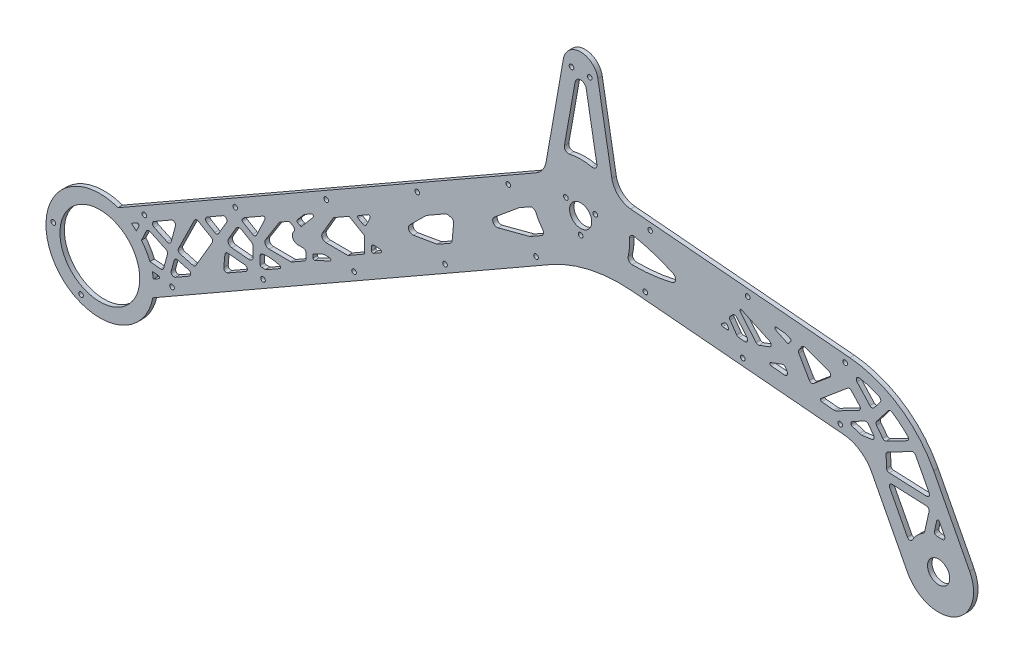
SolidWorks part; units mm, degrees
material "6061-T6 (SS)"
ref_plane "Front Plane" through (0, 0, 0) normal (0, 0, 1) x (1, 0, 0)
ref_plane "Top Plane" through (0, 0, 0) normal (0, 1, 0) x (1, 0, 0)
ref_plane "Right Plane" through (0, 0, 0) normal (1, 0, 0) x (0, 0, -1)
sketch "Reference Sketch" plane through (0, 0, 0) normal (0, 0, 1) x (1, 0, 0)
  line L0 (-343.92, -196.825) -> (0, 0) construction
  line L1 (-243.92, 103.175) -> (356.08, 103.175) construction
  line L2 (-243.92, 103.175) -> (-243.92, 0) construction
  line L3 (-243.92, 0) -> (356.08, 0) construction
  line L4 (356.08, 103.175) -> (356.08, 0) construction
  line L5 (0, 0) -> (256.08, -92.7116) construction
  line L6 (256.08, -92.7116) -> (56.08, -196.825) construction
  line L7 (256.08, -92.7116) -> (456.08, -196.825) construction
  line L8 (-343.92, -196.825) -> (56.08, -196.825) construction
  line L9 (56.08, -196.825) -> (456.08, -196.825) construction
  circle A1 centre (-343.92, -196.825) radius 100 construction
  circle A2 centre (56.08, -196.825) radius 100 construction
  circle A3 centre (456.08, -196.825) radius 100 construction
  circle A4 centre (-343.92, -196.825) radius 16.05 construction
  circle A5 centre (-343.92, -196.825) radius 28.55 construction
  circle A6 centre (-343.92, -196.825) radius 38.55 construction
  circle A7 centre (-343.92, -196.825) radius 33.55 construction
  point P13 (-343.92, -296.825)
  point P14 (556.08, -196.825)
  point P17 (-443.92, -196.825)
  dimension "D3" = 32.1
  dimension "D5" = 200
  dimension "D9" = 57.1
  dimension "D10" = 10
  dimension "D11" = 5
  dimension "D1" = 600
  dimension "D2" = 103.175
  dimension "D4" = 243.92
  dimension "D6" = 125
  dimension "D7" = 400
  dimension "D8" = 1000
sketch "Sketch2" plane through (0, 0, 0) normal (0, 0, 1) x (1, 0, 0)
  line L0 (-379.7168, -188.5069) -> (-32.0065, 10.4873)
  line L1 (-354.8814, -231.9028) -> (-21.5627, -41.1449)
  line L2 (-343.92, -196.825) -> (0, 0) construction
  line L3 (-184.3777, -76.7146) -> (-159.5423, -120.1104) construction
  line L4 (-24.685, 20.9013) -> (-12.3101, 91.0831)
  line L5 (12.3101, 91.0831) -> (22.322, 34.3028)
  line L6 (0, 98.4125) -> (0, 112.7) construction
  line L7 (-5.4848, 79.4125) -> (5.4848, 79.4125) construction
  line L8 (5.4848, 79.4125) -> (10.9697, 88.9125) construction
  line L9 (10.9697, 88.9125) -> (5.4848, 98.4125) construction
  line L10 (5.4848, 98.4125) -> (-5.4848, 98.4125) construction
  line L11 (-5.4848, 98.4125) -> (-10.9697, 88.9125) construction
  line L12 (-10.9697, 88.9125) -> (-5.4848, 79.4125) construction
  line L13 (-243.92, 103.175) -> (356.08, 103.175) construction
  line L14 (0, 88.9125) -> (0, 0) construction
  line L15 (35.7868, 21.9646) -> (192.5861, 8.2464)
  line L16 (252.5753, -31.8371) -> (278.2553, -81.1679)
  line L17 (233.9047, -104.2553) -> (208.2247, -54.9245)
  line L18 (36.8237, -28.3172) -> (188.2284, -41.5633)
  line L19 (0, 0) -> (192.5861, -16.8491) construction
  line L21 (-365.6311, -190.9191) -> (-338.0141, -175.1139) construction
  line L22 (-381.5729, -195.33) -> (-361.7045, -230.0467)
  line L23 (256.08, -92.7116) -> (56.08, -196.825) construction
  line L25 (-243.92, 0) -> (356.08, 0) construction
  circle A0 centre (0, 0) radius 7.9375
  circle A1 centre (-343.92, -196.825) radius 16.05
  arc A3 (-12.3101, 91.0831) -> (12.3101, 91.0831) centre (0, 88.9125) cw
  circle A4 centre (0, 88.9125) radius 6.5 construction
  circle A5 centre (-6.5, 88.9125) radius 1.65
  circle A6 centre (6.5, 88.9125) radius 1.65
  circle A7 centre (0, 88.9125) radius 9.5 construction
  arc A8 (252.5753, -31.8371) -> (192.5861, 8.2464) centre (186.0495, -66.4682) ccw
  circle A9 centre (256.08, -92.7116) radius 7.9375
  arc A10 (278.2553, -81.1679) -> (233.9047, -104.2553) centre (256.08, -92.7116) cw
  arc A11 (-21.5627, -41.1449) -> (36.8237, -28.3172) centre (28.1082, -127.9366) cw
  arc A12 (188.2284, -41.5633) -> (208.2247, -54.9245) centre (186.0495, -66.4682) cw
  arc A13 (22.322, 34.3028) -> (35.7868, 21.9646) centre (37.0941, 36.9075) ccw
  arc A14 (-32.0065, 10.4873) -> (-24.685, 20.9013) centre (-39.4572, 23.506) ccw
  circle A17 centre (-343.92, -196.825) radius 22.5 construction
  circle A18 centre (-365.6311, -190.9191) radius 1.65
  circle A19 centre (-338.0141, -175.1139) radius 1.65
  circle A20 centre (-322.2089, -202.7309) radius 1.65
  circle A21 centre (-349.8259, -218.5361) radius 1.65
  arc A27 (-379.7168, -188.5069) -> (-381.5729, -195.33) centre (-377.2333, -192.8465) ccw
  arc A28 (-361.7045, -230.0467) -> (-354.8814, -231.9028) centre (-357.3649, -227.5632) ccw
  circle A29 centre (-343.92, -196.825) radius 33.55 construction
  circle A32 centre (-343.92, -196.825) radius 38.55 construction
  point P16 (-171.96, -98.4125)
  point P64 (-343.92, -196.825)
  dimension "D1" = 15.875
  dimension "D2" = 32.1
  dimension "D3" = 45
  dimension "D5" = 13
  dimension "D6" = 3.3
  dimension "D7" = 6
  dimension "D12" = 50
  dimension "D14" = 100
  dimension "D16" = 15
  dimension "D17" = 5
  dimension "D18" = 25
  dimension "D19" = 3.3
  dimension "D15" = 4
  dimension "D4" = 50
  dimension "D8" = 19
  dimension "D9" = 14.2875
  dimension "D10" = 9.525
  dimension "D11" = 10
  dimension "D13" = 50
extrude "Base" add sketch "Sketch2" along normal blind 3.175
sketch "Sketch3" plane through (0, 0, 3.175) normal (0, 0, 1) x (1, 0, 0)
  line L0 (-343.92, -196.825) -> (0, 0) construction
  line L5 (0, 0) -> (197.3986, -17.2701) construction
  line L6 (192.5861, 8.2464) -> (35.7868, 21.9646) construction
  line L9 (36.8237, -28.3172) -> (188.2284, -41.5633) construction
  line L10 (-31.8958, -41.2976) -> (0, 0) construction
  line L11 (0, 0) -> (46.2693, -24.1244) construction
  circle A0 centre (-357.3649, -227.5632) radius 1.65
  circle A1 centre (-343.92, -196.825) radius 33.55 construction
  arc A2 (-361.7045, -230.0467) -> (-354.8814, -231.9028) centre (-357.3649, -227.5632) ccw construction
  circle A3 centre (-292.2711, -190.3101) radius 1.65
  circle A4 centre (-227.1773, -153.057) radius 1.65
  circle A5 centre (-162.0835, -115.8038) radius 1.65
  circle A6 centre (-96.9897, -78.5507) radius 1.65
  circle A7 centre (-31.8958, -41.2976) radius 1.65
  circle A8 centre (-312.1394, -155.5934) radius 1.65
  circle A9 centre (-377.2333, -192.8465) radius 1.65
  circle A10 centre (-247.0456, -118.3403) radius 1.65
  circle A11 centre (-181.9518, -81.0871) radius 1.65
  circle A12 centre (-116.858, -43.834) radius 1.65
  circle A13 centre (-51.7642, -6.5809) radius 1.65
  circle A14 centre (46.2693, -24.1244) radius 1.65
  circle A15 centre (116.0029, -30.2253) radius 1.65
  circle A16 centre (185.7366, -36.3262) radius 1.65
  circle A17 centre (189.2228, 3.5215) radius 1.65
  circle A18 centre (119.4892, 9.6224) radius 1.65
  circle A19 centre (49.7555, 15.7234) radius 1.65
  dimension "D1" = 3.3
  dimension "D2" = 6
  dimension "D3" = 5
  dimension "D5" = 3
  dimension "D4" = 75
  dimension "D6" = 70
extrude "Strut Holes" cut sketch "Sketch3" against normal through all
sketch "Sketch6" plane through (0, 0, 3.175) normal (0, 0, 1) x (1, 0, 0)
  line L0 (-315.2692, -197.7109) -> (-301.7593, -189.9792)
  line L1 (-354.8814, -231.9028) -> (-21.5627, -41.1449) construction
  line L2 (-289.845, -183.1607) -> (-279.9388, -177.4914)
  line L3 (-225.0683, -146.089) -> (-215.0659, -140.3647)
  line L4 (-202.4189, -105.5114) -> (-200.6862, -106.5205)
  line L5 (-330.4255, -170.6672) -> (-317.3783, -163.2003)
  line L6 (-32.0065, 10.4873) -> (-379.7168, -188.5069) construction
  line L7 (-315.9769, -164.4942) -> (-323.4022, -180.2613)
  line L8 (-325.3934, -181.4009) -> (-327.8261, -181.1787)
  line L9 (-302.165, -188.1154) -> (-317.5291, -186.7124)
  line L10 (-319.5204, -187.852) -> (-321.9207, -192.9489)
  line L11 (-295.5333, -171.6316) -> (-298.2962, -181.7883)
  line L12 (-300.4079, -183.2551) -> (-315.6625, -181.8621)
  line L13 (-317.2901, -179.0183) -> (-310.6415, -164.9005)
  line L14 (-307.9799, -163.9432) -> (-296.6111, -169.2972)
  line L15 (-280.4073, -173.8257) -> (-288.2923, -171.6808)
  line L16 (-290.7472, -173.0857) -> (-292.8686, -180.8843)
  line L17 (-292.7787, -149.122) -> (-305.2156, -156.2396)
  line L18 (-305.0743, -159.7848) -> (-295.766, -164.1685)
  line L19 (-292.984, -162.8841) -> (-289.8554, -151.3828)
  line L20 (-286.4122, -167.0105) -> (-277.4777, -169.4409)
  line L21 (-275.2245, -168.5176) -> (-263.487, -148.3649)
  line L22 (-264.2087, -145.6301) -> (-273.4911, -140.2238)
  line L23 (-276.2919, -141.0684) -> (-287.6814, -164.1971)
  line L24 (-267.3269, -134.556) -> (-255.9817, -128.0631)
  line L25 (-253.26, -130.8055) -> (-258.9575, -140.5878)
  line L26 (-261.6923, -141.3094) -> (-267.3401, -138.02)
  line L27 (-255.2613, -159.7424) -> (-254.4886, -151.2802)
  line L28 (-252.315, -149.4703) -> (-240.2297, -150.5739)
  line L29 (-292.2711, -190.3101) -> (-299.0066, -188.4038) construction
  line L30 (-252.2762, -161.6601) -> (-239.4181, -154.3014)
  line L31 (-246.5402, -131.1894) -> (-251.7948, -140.2114)
  line L32 (-249.4752, -144.7088) -> (-237.508, -145.8016)
  line L33 (-234.2352, -142.8254) -> (-234.2117, -136.6339)
  line L34 (-235.7018, -134.0302) -> (-242.4379, -130.1069)
  line L35 (-229.2226, -139.4963) -> (-229.2439, -145.1246)
  line L36 (-241.7536, -124.7193) -> (-234.6398, -128.8625)
  line L37 (-231.8238, -127.9864) -> (-225.7969, -115.1887)
  line L38 (-227.1983, -113.8948) -> (-240.4869, -121.4998)
  line L39 (-215.6688, -112.1749) -> (-225.38, -127.5855)
  line L40 (-222.8533, -132.1849) -> (-207.4544, -132.2434)
  line L41 (-206.4534, -131.9792) -> (-197.5057, -126.8584)
  line L42 (-196.4991, -125.1302) -> (-196.4845, -121.2849)
  line L43 (-198.4769, -119.2773) -> (-202.2607, -119.2629)
  line L44 (-205.6297, -113.1304) -> (-205.0269, -112.1739)
  line L45 (-205.7124, -109.3794) -> (-207.4618, -108.3605)
  line L46 (-209.4618, -108.3529) -> (-214.9702, -111.5053)
  line L47 (-223.2993, -137.1832) -> (-189.5978, -137.3112) construction
  line L48 (-199.4194, -106.3021) -> (-191.3609, -96.7721)
  line L49 (-192.6212, -95.2585) -> (-197.479, -98.0386)
  line L50 (-198.0128, -98.4831) -> (-202.6792, -104.0016)
  line L51 (-191.4798, -120.0542) -> (-191.4866, -121.8475)
  line L52 (-190.0674, -122.7592) -> (-179.2455, -117.7628)
  line L54 (-190.899, -119.1501) -> (-184.1308, -116.0253)
  line L55 (-183.2849, -115.8411) -> (-179.6609, -115.8549)
  line L56 (-166.4011, -107.9052) -> (-182.2049, -107.8452)
  line L57 (-184.7858, -103.3353) -> (-176.832, -89.6789)
  line L58 (-176.832, -89.6789) -> (-165.639, -83.2731)
  line L59 (-165.639, -83.2731) -> (-154.6405, -89.6789)
  line L60 (-154.6405, -89.6789) -> (-154.6842, -101.1996)
  line L61 (-154.6842, -101.1996) -> (-166.4011, -107.9052)
  line L62 (-176.832, -89.6789) -> (-166.4011, -107.9052) construction
  line L63 (-149.6667, -96.5998) -> (-149.6576, -94.1811)
  line L64 (-147.4757, -92.197) -> (-143.2847, -92.5797)
  line L65 (-142.8789, -94.4434) -> (-148.17, -97.4715)
  line L66 (-159.1247, -79.5451) -> (-152.014, -75.4756)
  line L67 (-150.6126, -76.7696) -> (-153.1821, -82.2258)
  line L68 (-155.9981, -83.102) -> (-159.1313, -81.2771)
  line L69 (-154.1121, -84.2004) -> (-149.6493, -91.9985) construction
  line L70 (-90.8199, -49.6985) -> (-91.8964, -61.4879)
  line L71 (-93.3939, -63.8188) -> (-101.9943, -68.7409)
  line L72 (-102.9747, -69.0935) -> (-119.6299, -71.9651)
  line L73 (-122.2529, -66.8794) -> (-110.6811, -55.3952)
  line L74 (-110.058, -54.9208) -> (-96.7247, -47.2901)
  line L75 (-94.4471, -46.9991) -> (-92.2866, -47.5868)
  line L76 (-102.4534, -69.0036) -> (-110.4008, -55.117) construction
  line L78 (-28.0968, -26.4494) -> (-35.8254, -30.8725)
  line L79 (-36.5501, -31.1694) -> (-59.134, -37.129)
  line L80 (-61.819, -31.9228) -> (-44.3172, -17.3499)
  line L81 (-43.8877, -17.0516) -> (-36.2746, -12.6946)
  line L82 (-44.1155, -17.182) -> (-36.1682, -31.0687) construction
  line L83 (-11.5997, 37.5245) -> (-3.9861, 80.7029)
  line L84 (3.9861, 80.7029) -> (11.5997, 37.5245)
  line L85 (22.322, 34.3028) -> (12.3101, 91.0831) construction
  line L86 (-12.3101, 91.0831) -> (-24.685, 20.9013) construction
  line L87 (192.5861, 8.2464) -> (35.7868, 21.9646) construction
  line L88 (36.8237, -28.3172) -> (188.2284, -41.5633) construction
  line L89 (-227.1773, -153.057) -> (-233.9128, -151.1507) construction
  line L90 (246.076, -72.9136) -> (249.254, -58.5784)
  line L91 (247.3887, -56.1475) -> (222.9622, -55.081)
  line L92 (221.1009, -58.0026) -> (233.7353, -82.273)
  line L93 (208.2247, -54.9245) -> (233.9047, -104.2553) construction
  line L94 (253.1337, -68.7997) -> (254.752, -61.5)
  line L95 (256.6153, -61.2547) -> (260.3456, -68.4206)
  line L96 (278.2553, -81.1679) -> (252.5753, -31.8371) construction
  line L97 (249.3108, -47.2228) -> (239.5975, -28.5637)
  line L98 (236.9, -27.7132) -> (219.5656, -36.7369)
  line L99 (218.491, -38.5982) -> (218.8608, -47.0688)
  line L100 (220.7717, -48.9796) -> (247.4495, -50.1444)
  line L101 (233.4135, -22.7639) -> (218.6181, -30.4658)
  line L102 (216.1079, -29.9093) -> (211.6718, -24.1281)
  line L103 (211.6718, -21.693) -> (220.0072, -10.8302)
  line L104 (209.6166, -31.3057) -> (205.7463, -26.2618)
  line L105 (203.2361, -25.7053) -> (194.0101, -30.5081)
  line L106 (193.4718, -31.3951) -> (193.4718, -32.4967)
  line L107 (201.069, -35.4569) -> (208.2909, -34.5061)
  line L108 (214.3031, -8.4078) -> (209.9577, -14.0708)
  line L109 (197.6887, -4.156) -> (206.8964, -14.2045)
  line L110 (193.6814, -11.6243) -> (199.5455, -18.0239)
  line L111 (198.9945, -21.1491) -> (182.8075, -29.5754)
  line L112 (181.1608, -29.903) -> (172.4826, -29.1438)
  line L113 (171.927, -27.3815) -> (190.9213, -11.4434)
  line L114 (178.1992, -11.0225) -> (166.5918, -20.7623)
  line L115 (163.5742, -20.2302) -> (156.048, -7.1944)
  line L116 (156.1417, -5.0472) -> (158.1885, -2.1242)
  line L117 (160.5108, -1.3919) -> (177.5977, -7.611)
  line L118 (146.6448, -20.9077) -> (147.747, -22.8167)
  line L119 (145.8406, -25.8091) -> (136.23, -24.9682)
  line L120 (135.9751, -23.0324) -> (144.2287, -20.0283)
  line L121 (134.9743, -13.819) -> (127.6718, -16.4769)
  line L122 (125.4557, -15.8831) -> (114.1985, -2.4673)
  line L123 (115.3872, -0.9182) -> (135.1355, -10.127)
  line L124 (139.4306, -1.096) -> (147.8318, -5.0136)
  line L125 (149.0736, -4.6809) -> (150.4259, -2.7496)
  line L126 (149.9488, -1.2363) -> (146.0985, 0.1651)
  line L127 (145.3339, 0.3346) -> (139.9404, 0.8065)
  line L128 (111.6605, -7.2212) -> (119.0455, -16.0223)
  line L129 (117.3391, -19.3002) -> (113.1162, -18.9308)
  line L130 (111.6522, -18.0855) -> (106.8775, -11.2665)
  line L131 (107.1016, -8.7052) -> (108.7142, -7.0926)
  line L132 (104.7039, -15.1361) -> (105.7554, -16.6377)
  line L133 (104.8491, -18.2075) -> (101.6773, -17.93)
  line L134 (101.2644, -16.0678) -> (103.3847, -14.8436)
  arc A0 (-317.584, -197.4764) -> (-320.5599, -195.9279) centre (-322.2089, -202.7309) ccw
  arc A1 (-291.1568, -183.3993) -> (-291.2348, -183.3872) centre (-292.2711, -190.3101) ccw
  arc A2 (-225.7665, -146.2006) -> (-228.1106, -146.1195) centre (-227.1773, -153.057) ccw
  arc A4 (-322.0747, -194.2209) -> (-322.0953, -194.053) centre (-343.92, -196.825) ccw
  arc A5 (-331.3132, -177.1382) -> (-331.3392, -173.0054) centre (-338.0141, -175.1139) ccw
  arc A6 (-329.0005, -180.6569) -> (-330.6088, -179.309) centre (-343.92, -196.825) ccw
  arc A8 (-227.5555, -137.5318) -> (-215.2363, -138.5515) centre (-223.3943, -162.1831) cw
  arc A9 (-241.9747, -123.1658) -> (-241.1717, -122.1478) centre (-247.0456, -118.3403) ccw
  arc A10 (-32.0383, -14.0906) -> (-27.2511, -21.9631) centre (0, 0) ccw
  arc A11 (-251.7948, -140.2114) -> (-249.4752, -144.7088) centre (-249.2024, -141.7213) ccw
  arc A12 (-225.38, -127.5855) -> (-222.8533, -132.1849) centre (-222.8419, -129.1849) ccw
  arc A13 (-182.2049, -107.8452) -> (-184.7858, -103.3353) centre (-182.1935, -104.8452) cw
  arc A14 (-119.6299, -71.9651) -> (-122.2529, -66.8794) centre (-120.1396, -69.0087) cw
  arc A15 (-59.134, -37.129) -> (-61.819, -31.9228) centre (-59.8994, -34.2283) cw
  arc A16 (-7.9627, 34.0822) -> (7.9627, 34.0822) centre (0, 0) cw
  arc A17 (-3.9861, 80.7029) -> (3.9861, 80.7029) centre (0, 80) cw
  arc A18 (34.8636, 3.0867) -> (34.0029, -8.2948) centre (0, 0) cw
  arc A19 (38.4335, 6.2944) -> (66.0977, -2.7713) centre (15.1723, -111.4295) cw
  arc A20 (66.0977, -2.7713) -> (65.4856, -8.7407) centre (64.749, -5.6491) cw
  arc A21 (36.898, -12.0057) -> (65.4856, -8.7407) centre (37.6733, 107.9918) ccw
  arc A22 (245.141, -74.2025) -> (237.26, -82.3165) centre (256.08, -92.7116) ccw
  arc A23 (258.3595, -71.3328) -> (255.1708, -71.2308) centre (256.08, -92.7116) ccw
  arc A24 (222.6875, -10.3732) -> (233.9189, -19.5905) centre (186.0495, -66.4682) cw
  arc A25 (252.5753, -31.8371) -> (192.5861, 8.2464) centre (186.0495, -66.4682) ccw construction
  arc A26 (194.2312, -33.4673) -> (199.4914, -35.2382) centre (186.0495, -66.4682) cw
  arc A27 (208.2247, -54.9245) -> (188.2284, -41.5633) centre (186.0495, -66.4682) ccw construction
  arc A28 (213.5369, -5.3663) -> (199.5667, -0.8459) centre (186.0495, -66.4682) ccw
  arc A29 (218.8608, -47.0688) -> (220.7717, -48.9796) centre (220.8589, -46.9815) ccw
  arc A30 (239.5975, -28.5637) -> (236.9, -27.7132) centre (237.8235, -29.4872) ccw
  arc A31 (219.5656, -36.7369) -> (218.491, -38.5982) centre (220.4891, -38.5109) ccw
  arc A32 (127.6718, -16.4769) -> (125.4557, -15.8831) centre (126.9878, -14.5975) cw
  arc A33 (-240.4869, -121.4998) -> (-241.1717, -122.1478) centre (-239.4934, -123.2356) ccw
  arc A34 (-234.6398, -128.8625) -> (-231.8238, -127.9864) centre (-233.6332, -127.1343) ccw
  arc A35 (-229.2226, -139.4963) -> (-227.5555, -137.5318) centre (-227.2226, -139.5039) cw
  arc A36 (-315.2692, -197.7109) -> (-317.584, -197.4764) centre (-316.2626, -195.9751) cw
  arc A37 (-322.0747, -194.2209) -> (-320.5599, -195.9279) centre (-320.0887, -193.9842) ccw
  arc A38 (-321.9207, -192.9489) -> (-322.0953, -194.053) centre (-320.1113, -193.801) ccw
  arc A39 (-317.5291, -186.7124) -> (-319.5204, -187.852) centre (-317.711, -188.7042) ccw
  arc A40 (-323.4022, -180.2613) -> (-325.3934, -181.4009) centre (-325.2116, -179.4092) cw
  arc A41 (-327.8261, -181.1787) -> (-329.0005, -180.6569) centre (-327.6442, -179.187) cw
  arc A42 (-331.3132, -177.1382) -> (-330.6088, -179.309) centre (-329.3986, -177.7166) ccw
  arc A43 (-330.4255, -170.6672) -> (-331.3392, -173.0054) centre (-329.4321, -172.403) ccw
  arc A44 (-315.6625, -181.8621) -> (-317.2901, -179.0183) centre (-315.4807, -179.8704) cw
  arc A45 (-298.2962, -181.7883) -> (-300.4079, -183.2551) centre (-300.226, -181.2634) cw
  arc A46 (-289.845, -183.1607) -> (-291.1568, -183.3993) centre (-290.8384, -181.4248) cw
  arc A47 (-292.8686, -180.8843) -> (-291.2348, -183.3872) centre (-290.9387, -181.4092) ccw
  arc A48 (-280.4073, -173.8257) -> (-279.9388, -177.4914) centre (-280.9322, -175.7556) cw
  arc A49 (-288.2923, -171.6808) -> (-290.7472, -173.0857) centre (-288.8173, -173.6107) ccw
  arc A50 (-295.5333, -171.6316) -> (-296.6111, -169.2972) centre (-297.4632, -171.1066) ccw
  arc A51 (-310.6415, -164.9005) -> (-307.9799, -163.9432) centre (-308.8321, -165.7526) cw
  arc A52 (-305.2156, -156.2396) -> (-305.0743, -159.7848) centre (-304.2222, -157.9754) ccw
  arc A53 (-292.7787, -149.122) -> (-289.8554, -151.3828) centre (-291.7853, -150.8578) cw
  arc A54 (-295.766, -164.1685) -> (-292.984, -162.8841) centre (-294.9139, -162.3591) ccw
  arc A55 (-286.4122, -167.0105) -> (-287.6814, -164.1971) centre (-285.8872, -165.0807) cw
  arc A56 (-277.4777, -169.4409) -> (-275.2245, -168.5176) centre (-276.9527, -167.511) ccw
  arc A57 (-263.487, -148.3649) -> (-264.2087, -145.6301) centre (-265.2153, -147.3583) ccw
  arc A58 (-273.4911, -140.2238) -> (-276.2919, -141.0684) centre (-274.4977, -141.952) ccw
  arc A59 (-267.3269, -134.556) -> (-267.3401, -138.02) centre (-266.3335, -136.2918) ccw
  arc A60 (-258.9575, -140.5878) -> (-261.6923, -141.3094) centre (-260.6857, -139.5812) cw
  arc A61 (-254.4886, -151.2802) -> (-252.315, -149.4703) centre (-252.4969, -151.462) cw
  arc A62 (-255.2613, -159.7424) -> (-252.2762, -161.6601) centre (-253.2696, -159.9243) ccw
  arc A63 (-239.4181, -154.3014) -> (-240.2297, -150.5739) centre (-240.4115, -152.5656) ccw
  arc A64 (-255.9817, -128.0631) -> (-253.26, -130.8055) centre (-254.9883, -129.7989) cw
  arc A65 (-207.4544, -132.2434) -> (-206.4534, -131.9792) centre (-207.4468, -130.2434) ccw
  arc A66 (-214.9702, -111.5053) -> (-215.6688, -112.1749) centre (-213.9767, -113.2412) ccw
  arc A67 (-207.4618, -108.3605) -> (-209.4618, -108.3529) centre (-208.4684, -110.0887) ccw
  arc A68 (-205.0269, -112.1739) -> (-205.7124, -109.3794) centre (-206.719, -111.1076) ccw
  arc A69 (-202.2607, -119.2629) -> (-205.6297, -113.1304) centre (-202.2456, -115.263) cw
  arc A70 (-196.4845, -121.2849) -> (-198.4769, -119.2773) centre (-198.4845, -121.2773) ccw
  arc A71 (-197.5057, -126.8584) -> (-196.4991, -125.1302) centre (-198.4991, -125.1226) ccw
  arc A72 (-184.1308, -116.0253) -> (-183.2849, -115.8411) centre (-183.2925, -117.8411) cw
  arc A73 (-197.479, -98.0386) -> (-198.0128, -98.4831) centre (-196.4856, -99.7744) ccw
  arc A74 (-149.6576, -94.1811) -> (-147.4757, -92.197) centre (-147.6576, -94.1887) cw
  arc A75 (-153.1821, -82.2258) -> (-155.9981, -83.102) centre (-154.9915, -81.3737) cw
  arc A76 (-90.8199, -49.6985) -> (-92.2866, -47.5868) centre (-92.8116, -49.5167) ccw
  arc A77 (111.6605, -7.2212) -> (108.7142, -7.0926) centre (110.1284, -8.5068) ccw
  arc A78 (106.8775, -11.2665) -> (107.1016, -8.7052) centre (108.5158, -10.1194) cw
  arc A79 (113.1162, -18.9308) -> (111.6522, -18.0855) centre (113.2905, -16.9384) cw
  arc A80 (119.0455, -16.0223) -> (117.3391, -19.3002) centre (117.5134, -17.3078) cw
  arc A81 (134.9743, -13.819) -> (135.1355, -10.127) centre (134.2903, -11.9396) ccw
  arc A82 (146.6448, -20.9077) -> (144.2287, -20.0283) centre (144.9128, -21.9077) ccw
  arc A83 (147.747, -22.8167) -> (145.8406, -25.8091) centre (146.0149, -23.8167) cw
  arc A84 (156.048, -7.1944) -> (156.1417, -5.0472) centre (157.78, -6.1944) cw
  arc A85 (158.1885, -2.1242) -> (160.5108, -1.3919) centre (159.8268, -3.2713) cw
  arc A86 (178.1992, -11.0225) -> (177.5977, -7.611) centre (176.9136, -9.4904) ccw
  arc A87 (166.5918, -20.7623) -> (163.5742, -20.2302) centre (165.3062, -19.2302) cw
  arc A88 (193.6814, -11.6243) -> (190.9213, -11.4434) centre (192.2068, -12.9755) ccw
  arc A89 (199.5455, -18.0239) -> (198.9945, -21.1491) centre (198.071, -19.375) cw
  arc A90 (209.9577, -14.0708) -> (206.8964, -14.2045) centre (208.371, -12.8533) cw
  arc A91 (213.5369, -5.3663) -> (214.3031, -8.4078) centre (212.7164, -7.1903) cw
  arc A92 (233.9189, -19.5905) -> (233.4135, -22.7639) centre (232.49, -20.9899) cw
  arc A93 (222.6875, -10.3732) -> (220.0072, -10.8302) centre (221.5939, -12.0477) ccw
  arc A94 (211.6718, -24.1281) -> (211.6718, -21.693) centre (213.2585, -22.9105) cw
  arc A95 (218.6181, -30.4658) -> (216.1079, -29.9093) centre (217.6946, -28.6918) cw
  arc A96 (205.7463, -26.2618) -> (203.2361, -25.7053) centre (204.1595, -27.4793) ccw
  arc A97 (209.6166, -31.3057) -> (208.2909, -34.5061) centre (208.0299, -32.5232) cw
  arc A98 (246.076, -72.9136) -> (245.141, -74.2025) centre (244.1234, -72.4807) cw
  arc A99 (249.254, -58.5784) -> (247.3887, -56.1475) centre (247.3014, -58.1456) ccw
  arc A100 (222.9622, -55.081) -> (221.1009, -58.0026) centre (222.8749, -57.0791) ccw
  arc A101 (233.7353, -82.273) -> (237.26, -82.3165) centre (235.5093, -81.3495) ccw
  arc A102 (260.3456, -68.4206) -> (258.3595, -71.3328) centre (258.5716, -69.344) cw
  arc A103 (253.1337, -68.7997) -> (255.1708, -71.2308) centre (255.0863, -69.2326) ccw
  arc A104 (249.3108, -47.2228) -> (247.4495, -50.1444) centre (247.5367, -48.1463) cw
  arc A105 (199.5667, -0.8459) -> (197.6887, -4.156) centre (199.1632, -2.8048) ccw
  arc A106 (-215.2363, -138.5515) -> (-215.0659, -140.3647) centre (-215.5626, -139.4968) cw
  arc A107 (-301.7593, -189.9792) -> (-302.165, -188.1154) centre (-302.256, -189.1113) ccw
  arc A108 (-317.3783, -163.2003) -> (-315.9769, -164.4942) centre (-316.8815, -164.0682) cw
  arc A109 (-225.7969, -115.1887) -> (-227.1983, -113.8948) centre (-226.7016, -114.7627) ccw
  arc A110 (-241.7536, -124.7193) -> (-241.9747, -123.1658) centre (-241.2503, -123.8551) cw
  arc A111 (-225.7665, -146.2006) -> (-225.0683, -146.089) centre (-225.565, -145.2211) ccw
  arc A112 (-229.2439, -145.1246) -> (-228.1106, -146.1195) centre (-228.2439, -145.1284) ccw
  arc A113 (-202.4189, -105.5114) -> (-202.6792, -104.0016) centre (-201.9156, -104.6473) cw
  arc A114 (-200.6862, -106.5205) -> (-199.4194, -106.3021) centre (-200.183, -105.6564) ccw
  arc A115 (-191.4798, -120.0542) -> (-190.899, -119.1501) centre (-190.4798, -120.058) cw
  arc A116 (-191.4866, -121.8475) -> (-190.0674, -122.7592) centre (-190.4866, -121.8513) ccw
  arc A117 (-191.3609, -96.7721) -> (-192.6212, -95.2585) centre (-192.1245, -96.1264) ccw
  arc A118 (-179.2455, -117.7628) -> (-179.6609, -115.8549) centre (-179.6647, -116.8549) ccw
  arc A119 (-152.014, -75.4756) -> (-150.6126, -76.7696) centre (-151.5173, -76.3435) cw
  arc A120 (-159.1247, -79.5451) -> (-159.1313, -81.2771) centre (-158.628, -80.413) ccw
  arc A121 (-149.6667, -96.5998) -> (-148.17, -97.4715) centre (-148.6667, -96.6036) ccw
  arc A122 (-143.2847, -92.5797) -> (-142.8789, -94.4434) centre (-143.3756, -93.5755) cw
  arc A123 (101.6773, -17.93) -> (101.2644, -16.0678) centre (101.7644, -16.9338) cw
  arc A124 (104.7039, -15.1361) -> (103.3847, -14.8436) centre (103.8847, -15.7096) ccw
  arc A125 (105.7554, -16.6377) -> (104.8491, -18.2075) centre (104.9362, -17.2113) cw
  arc A126 (114.1985, -2.4673) -> (115.3872, -0.9182) centre (114.9646, -1.8245) cw
  arc A127 (136.23, -24.9682) -> (135.9751, -23.0324) centre (136.3171, -23.972) cw
  arc A128 (139.4306, -1.096) -> (139.9404, 0.8065) centre (139.8532, -0.1897) cw
  arc A129 (172.4826, -29.1438) -> (171.927, -27.3815) centre (172.5698, -28.1476) cw
  arc A130 (194.0101, -30.5081) -> (193.4718, -31.3951) centre (194.4718, -31.3951) ccw
  arc A131 (193.4718, -32.4967) -> (194.2312, -33.4673) centre (194.4718, -32.4967) ccw
  arc A132 (254.752, -61.5) -> (256.6153, -61.2547) centre (255.7283, -61.7164) cw
  arc A133 (146.0985, 0.1651) -> (145.3339, 0.3346) centre (145.0724, -2.654) ccw
  arc A134 (199.4914, -35.2382) -> (201.069, -35.4569) centre (200.6774, -32.4826) ccw
  arc A135 (182.8075, -29.5754) -> (181.1608, -29.903) centre (181.4223, -26.9144) cw
  arc A136 (-7.9627, 34.0822) -> (-11.5997, 37.5245) centre (-8.6452, 37.0035) cw
  arc A137 (7.9627, 34.0822) -> (11.5997, 37.5245) centre (8.6452, 37.0035) ccw
  arc A138 (34.8636, 3.0867) -> (38.4335, 6.2944) centre (37.8519, 3.3513) cw
  arc A139 (34.0029, -8.2948) -> (36.898, -12.0057) centre (36.9174, -9.0058) ccw
  arc A140 (-35.8254, -30.8725) -> (-36.5501, -31.1694) centre (-37.3155, -28.2687) cw
  arc A141 (-44.3172, -17.3499) -> (-43.8877, -17.0516) centre (-42.3976, -19.6554) cw
  arc A142 (-32.0383, -14.0906) -> (-36.2746, -12.6946) centre (-34.7845, -15.2984) ccw
  arc A143 (-27.2511, -21.9631) -> (-28.0968, -26.4494) centre (-29.5869, -23.8456) cw
  arc A144 (-96.7247, -47.2901) -> (-94.4471, -46.9991) centre (-95.2346, -49.8939) cw
  arc A145 (-91.8964, -61.4879) -> (-93.3939, -63.8188) centre (-94.884, -61.2151) cw
  arc A146 (-110.6811, -55.3952) -> (-110.058, -54.9208) centre (-108.5679, -57.5245) cw
  arc A147 (-101.9943, -68.7409) -> (-102.9747, -69.0935) centre (-103.4845, -66.1371) cw
  arc A148 (-246.5402, -131.1894) -> (-242.4379, -130.1069) centre (-243.9478, -132.6992) cw
  arc A149 (-234.2117, -136.6339) -> (-235.7018, -134.0302) centre (-237.2117, -136.6225) ccw
  arc A150 (-237.508, -145.8016) -> (-234.2352, -142.8254) centre (-237.2352, -142.8141) ccw
  arc A151 (150.4259, -2.7496) -> (149.9488, -1.2363) centre (149.6067, -2.176) ccw
  arc A152 (147.8318, -5.0136) -> (149.0736, -4.6809) centre (148.2544, -4.1073) ccw
  point P98 (-116.858, -43.834)
  point P110 (-254.1648, -144.2806)
  point P113 (-228.2654, -132.1643)
  point P143 (34.9003, -2.6394)
  point P203 (218.9408, -48.8997)
  point P206 (238.674, -26.7897)
  point P211 (126.3559, -16.9559)
  point P214 (-240.9361, -121.7569)
  point P217 (-232.7537, -129.961)
  point P220 (-229.2164, -137.8704)
  point P229 (-318.9237, -186.5851)
  point P232 (-323.9988, -181.5282)
  point P235 (-328.5183, -181.1155)
  point P240 (-331.9839, -171.5591)
  point P247 (-290.5028, -183.5371)
  point P252 (-275.7482, -175.0931)
  point P255 (-290.2222, -171.1558)
  point P262 (-308.5502, -158.1479)
  point P265 (-288.588, -146.7237)
  point P268 (-293.6097, -165.184)
  point P271 (-288.7533, -166.3737)
  point P278 (-275.3444, -139.1443)
  point P281 (-270.3335, -136.2766)
  point P288 (-255.6107, -163.5684)
  point P294 (-249.5035, -124.3556)
  point P297 (-206.9185, -132.2454)
  point P300 (-215.403, -111.753)
  point P303 (-208.4596, -107.7794)
  point P308 (-209.4769, -119.2355)
  point P311 (-196.4769, -119.2849)
  point P314 (-196.5035, -126.2849)
  point P329 (110.2575, -5.5492)
  point P334 (112.1872, -18.8495)
  point P337 (122.1491, -19.721)
  point P340 (139.5116, -12.1676)
  point P345 (149.6679, -26.1439)
  point P350 (159.0687, -0.8671)
  point P353 (180.8529, -8.7958)
  point P356 (164.7659, -22.2944)
  point P363 (208.5067, -15.9618)
  point P366 (215.8118, -6.4415)
  point P369 (235.7568, -21.544)
  point P374 (210.7376, -22.9105)
  point P377 (217.1296, -31.2407)
  point P380 (204.7246, -24.9304)
  point P383 (211.7254, -34.054)
  point P390 (219.5014, -54.9299)
  point P393 (235.6626, -85.9753)
  point P396 (262.2729, -72.1228)
  point P401 (250.9103, -50.2955)
  point P406 (-213.2581, -139.3301)
  point P412 (-314.6256, -161.6249)
  point P415 (-224.4456, -112.3194)
  point P420 (-225.4089, -146.284)
  point P423 (-229.2487, -146.3704)
  point P426 (-203.4487, -104.9116)
  point P431 (-191.4774, -119.4171)
  point P434 (-191.4925, -123.4171)
  point P437 (-187.699, -92.4415)
  point P440 (-175.1502, -115.872)
  point P447 (-149.6733, -98.3319)
  point P450 (-140.1262, -92.8681)
  point P453 (98.5177, -17.6536)
  point P458 (106.9854, -18.3944)
  point P463 (131.7364, -24.5751)
  point P468 (170.0776, -28.9333)
  point P471 (193.4718, -30.7883)
  point P474 (193.4718, -33.2883)
  point P477 (255.3467, -58.8176)
  point P484 (182.0319, -29.9792)
  point P491 (34.2849, 7.0387)
  point P494 (32.91, -11.9136)
  point P505 (-24.8853, -24.6115)
  point P508 (-95.6462, -46.6729)
  point P511 (-92.0384, -63.0431)
  point P524 (-234.2477, -146.0993)
  point P527 (151.1734, -1.682)
  point P530 (148.5923, -5.3682)
  dimension "D1" = 14
  dimension "D2" = 10
  dimension "D3" = 2
  dimension "D5" = 22
  dimension "D6" = 9
  dimension "D12" = 5
  dimension "D19" = 7
  dimension "D31" = 7
  dimension "D40" = 25
  dimension "D44" = 19
  dimension "D62" = 5
  dimension "D92" = 35
  dimension "D96" = 3
  dimension "D97" = 10
  dimension "D100" = 15
  dimension "D104" = 30
  dimension "D105" = 120
  dimension "D107" = 43
  dimension "D116" = 65
  dimension "D117" = 8
  dimension "D127" = 9
  dimension "D128" = 6
  dimension "D171" = 2
  dimension "D172" = 1
  dimension "D173" = 3
  dimension "D174" = 1
  dimension "D175" = 4
  dimension "D7" = 35
  dimension "D8" = 35
  dimension "D9" = 20
  dimension "D10" = 22
  dimension "D11" = 20
  dimension "D13" = 5
  dimension "D14" = 45
  dimension "D15" = 45
  dimension "D16" = 17
  dimension "D17" = 15
  dimension "D18" = 5
  dimension "D20" = 55
  dimension "D21" = 5
  dimension "D22" = 45
  dimension "D23" = 23
  dimension "D24" = 34
  dimension "D25" = 60
  dimension "D26" = 5
  dimension "D27" = 5
  dimension "D28" = 5
  dimension "D29" = 30
  dimension "D30" = 24
  dimension "D32" = 55
  dimension "D33" = 35
  dimension "D34" = 25
  dimension "D35" = 5
  dimension "D36" = 6
  dimension "D37" = 60
  dimension "D38" = 5
  dimension "D39" = 20
  dimension "D41" = 11
  dimension "D42" = 35
  dimension "D43" = 60
  dimension "D45" = 19.5
  dimension "D46" = 5
  dimension "D47" = 5
  dimension "D48" = 30
  dimension "D49" = 5
  dimension "D50" = 14
  dimension "D51" = 13
  dimension "D52" = 8.5
  dimension "D53" = 60
  dimension "D54" = 12
  dimension "D55" = 7
  dimension "D56" = 22
  dimension "D57" = 28
  dimension "D58" = 60
  dimension "D59" = 15
  dimension "D60" = 8
  dimension "D61" = 13
  dimension "D63" = 12
  dimension "D64" = 20
  dimension "D65" = 5
  dimension "D66" = 65
  dimension "D67" = 25
  dimension "2" = 18
  dimension "D68" = 8
  dimension "D69" = 4
  dimension "D70" = 14
  dimension "D71" = 15
  dimension "D72" = 13.5
  dimension "D73" = 60
  dimension "D74" = 60
  dimension "D75" = 8
  dimension "D76" = 5
  dimension "D77" = 35
  dimension "D78" = 0.5076
  dimension "D79" = 5
  dimension "D80" = 11
  dimension "D81" = 35
  dimension "D82" = 16
  dimension "D83" = 18
  dimension "D84" = 55
  dimension "D85" = 45
  dimension "D86" = 20
  dimension "D87" = 15
  dimension "D88" = 12
  dimension "D89" = 17
  dimension "D90" = 16
  dimension "D91" = 18
  dimension "D93" = 15
  dimension "D94" = 10
  dimension "D95" = 13
  dimension "D98" = 10
  dimension "D99" = 80
  dimension "D101" = 16
  dimension "D102" = 22
  dimension "D103" = 22
  dimension "D106" = 7
  dimension "D108" = 10
  dimension "D109" = 40
  dimension "D110" = 10
  dimension "D111" = 6
  dimension "D112" = 60
  dimension "D113" = 35
  dimension "D114" = 15
  dimension "D115" = 6
  dimension "D118" = 26.5
  dimension "D119" = 6
  dimension "D120" = 85
  dimension "D121" = 85
  dimension "D122" = 32
  dimension "D123" = 21
  dimension "D124" = 80
  dimension "D125" = 75
  dimension "D126" = 6
  dimension "D129" = 10.5
  dimension "D130" = 80
  dimension "D131" = 12
  dimension "D132" = 8
  dimension "D133" = 6
  dimension "D134" = 2.5
  dimension "D135" = 100
  dimension "D136" = 11.5
  dimension "D137" = 60
  dimension "D138" = 11
  dimension "D139" = 45
  dimension "D140" = 12
  dimension "D141" = 8.5
  dimension "D142" = 12
  dimension "D143" = 18
  dimension "D144" = 80
  dimension "D145" = 21
  dimension "D146" = 60
  dimension "D147" = 60
  dimension "D148" = 15
  dimension "D149" = 12
  dimension "D150" = 18
  dimension "D151" = 25
  dimension "D152" = 9
  dimension "D153" = 12
  dimension "D154" = 6
  dimension "D155" = 15
  dimension "D156" = 20
  dimension "D157" = 10
  dimension "D158" = 13.5
  dimension "D159" = 4.5
  dimension "D160" = 45
  dimension "D161" = 14
  dimension "D162" = 5
  dimension "D163" = 10
  dimension "D164" = 16
  dimension "D165" = 50
  dimension "D166" = 18.5
  dimension "D167" = 50
  dimension "D168" = 4
  dimension "D169" = 8.5
  dimension "D170" = 35
extrude "Lightening Holes" cut sketch "Sketch6" against normal through all
sketch "Sketch7" plane through (0, 0, 3.175) normal (0, 0, 1) x (1, 0, 0)
  circle A13 centre (-357.3649, -227.5632) radius 1.65 construction
  circle A15 centre (-377.2333, -192.8465) radius 1.65 construction
  circle A16 centre (-343.92, -196.825) radius 38.55 construction
  circle A17 centre (-343.92, -196.825) radius 28.55 construction
  circle A26 centre (-357.3649, -227.5632) radius 1.65
  circle A27 centre (-377.2333, -192.8465) radius 1.65
  circle A28 centre (-343.92, -196.825) radius 38.55
  circle A29 centre (-343.92, -196.825) radius 28.55
extrude "Inner Mod Extrusion" add sketch "Sketch7" against normal up to surface (3.175 mm away) up to face at (-260.7262, -135.4767, 0)
extrude "Inner Mod Cut" cut sketch "Sketch7<2>" against normal through all contours A29 region at (-343.92, -196.825, 3.175)
sketch "Sketch7<2>" plane through (0, 0, 3.175) normal (0, 0, 1) x (1, 0, 0) same geometry as "Sketch7"
sketch "Sketch8" plane through (0, 0, 3.175) normal (0, 0, 1) x (1, 0, 0)
  circle A0 centre (-10.5, 6.0622) radius 1.65
  circle A1 centre (10.5, 6.0622) radius 1.65
  circle A2 centre (0, -12.1244) radius 1.65
  point P0 (0, 0)
  point P1 (0, 0)
  point P14 (0, 0)
  dimension "D2" = 3.3
  dimension "D1" = 21
  dimension "D3" = 3
extrude "Cut-Extrude1" cut sketch "Sketch8" against normal through all
